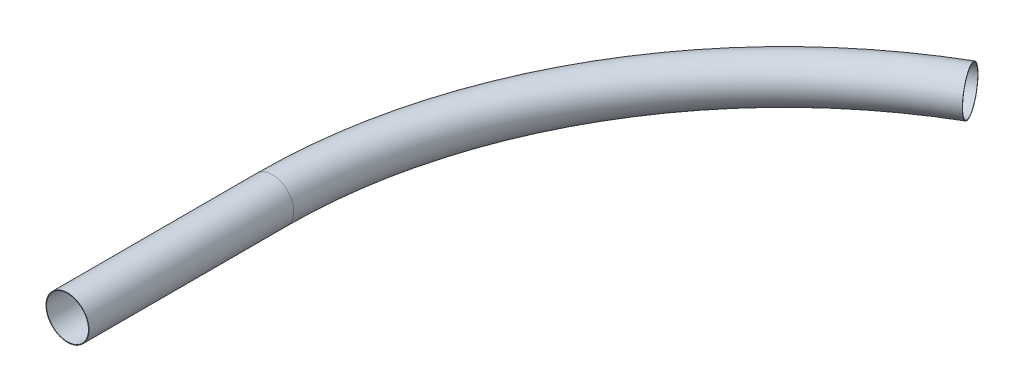
SolidWorks part; units mm, degrees
ref_plane "前视基准面" through (0, 0, 0) normal (0, 0, 1) x (1, 0, 0)
ref_plane "上视基准面" through (0, 0, 0) normal (0, 1, 0) x (1, 0, 0)
ref_plane "右视基准面" through (0, 0, 0) normal (1, 0, 0) x (0, 0, -1)
sketch "草图1" plane through (0, 0, 0) normal (0, 0, 1) x (1, 0, 0)
  line L0 (231, 0) -> (-231, 0) construction
  circle A0 centre (0, 0) radius 205
  circle A1 centre (0, 0) radius 210
  dimension "D1" = 410
  dimension "D2" = 420
sketch "草图2" plane through (0, 0, 0) normal (0, 1, 0) x (1, 0, 0)
  line L0 (0, 0) -> (0, 1000)
  arc A0 (0, 1000) -> (2491.5234, 5325.2219) centre (5000, 1000) cw
  dimension "D2" = 5000
  dimension "D1" = 1000
sweep "扫描1" add profiles "草图1" path "草图2"
sketch "草图3" plane through (0, 0, 0) normal (0, 0, 1) x (1, 0, 0)
  circle A0 centre (0, 0) radius 205 construction
  circle A1 centre (0, 0) radius 210
  circle A2 centre (0, 0) radius 210
  circle A3 centre (0, 0) radius 205
  dimension "D1" = 0
extrude "凸台-拉伸1" add sketch "草图3" along normal blind 1000
